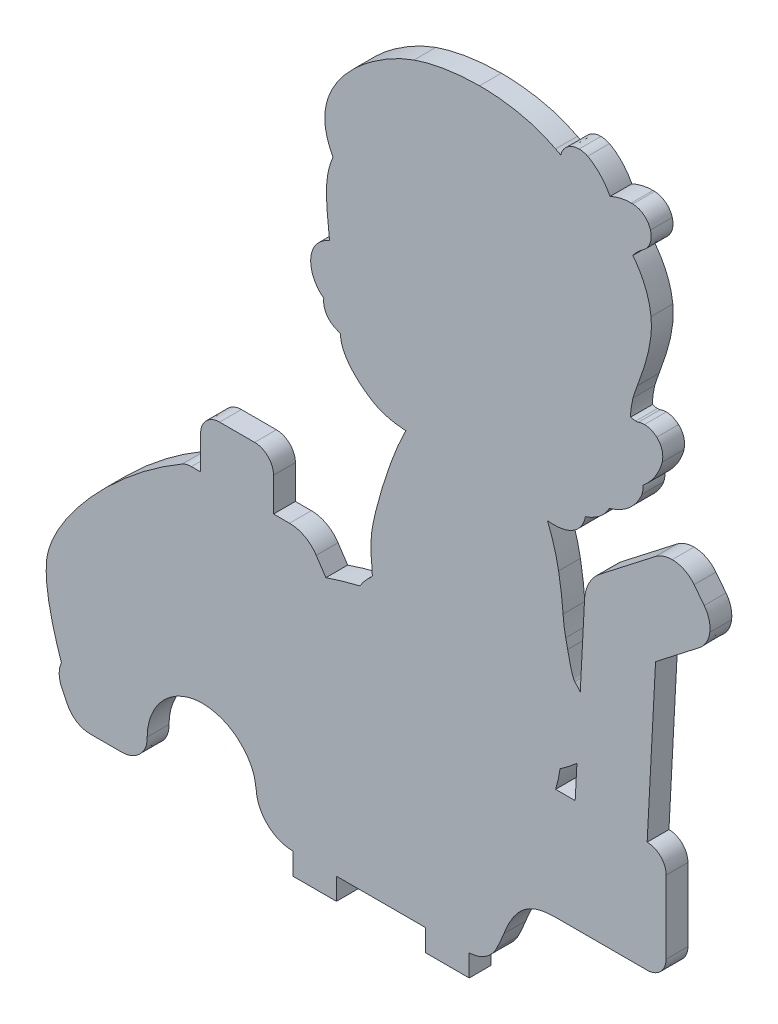
SolidWorks part; units mm, degrees
ref_plane "Front Plane" through (0, 0, 0) normal (0, 0, 1) x (1, 0, 0)
ref_plane "Top Plane" through (0, 0, 0) normal (0, 1, 0) x (1, 0, 0)
ref_plane "Right Plane" through (0, 0, 0) normal (1, 0, 0) x (0, 0, -1)
sketch "Model" plane through (0, 0, 0) normal (0, 0, 1) x (1, 0, 0)
  line L0 (289.9985, -383.7753) -> (289.8149, -387.2738)
  line L1 (289.8149, -387.2738) -> (287.7513, -387.2738)
  line L2 (263.5287, -380.0569) -> (262.5101, -378.5259)
  line L3 (259.6897, -377.0034) -> (258.0098, -377.0034)
  line L4 (258.0098, -377.0034) -> (258.0098, -373.459)
  line L5 (256.0138, -371.4557) -> (252.3171, -371.4557)
  line L6 (250.3211, -373.459) -> (250.3211, -377.0034)
  line L7 (250.3211, -377.0034) -> (249.3468, -377.0034)
  line L8 (235.6813, -404.0488) -> (236.2843, -405.2726)
  line L9 (238.6679, -406.7577) -> (242.0233, -406.7577)
  line L10 (260.043, -406.7577) -> (278.5385, -406.7577)
  line L11 (287.9321, -398.9652) -> (297.408, -398.9652)
  line L12 (299.404, -396.9619) -> (299.404, -389.2771)
  line L13 (297.408, -387.2738) -> (297.4036, -387.2738)
  line L14 (297.4036, -387.2738) -> (298.292, -370.3419)
  line L15 (298.292, -370.3419) -> (302.8973, -366.7692)
  line L16 (303.4169, -362.6517) -> (302.3566, -361.2835)
  line L17 (298.2586, -360.7635) -> (292.4293, -365.2857)
  line L18 (290.8054, -368.394) -> (290.3486, -377.102)
  line L19 (288.2912, -329.0773) -> (287.7488, -328.7908)
  spline S0 degree 3 poles (288.2176, -385.16) (288.7789, -384.7782) (289.421, -384.2968) (289.9985, -383.7753) knots 0 0 0 0 1 1 1 1
  spline S1 degree 3 poles (287.7513, -387.2738) (288.0017, -386.4926) (288.1406, -385.7436) (288.2176, -385.16) knots 3 3 3 3 4 4 4 4
  spline S2 degree 3 poles (279.7281, -327.0358) (277.2927, -327.0357) (274.84, -327.4258) (272.8218, -328.1341) knots 1 1 1 1 2 2 2 2
  spline S3 degree 3 poles (272.8218, -328.1341) (270.6039, -328.9125) (268.2296, -330.4012) (266.4707, -332.1165) knots 2 2 2 2 3 3 3 3
  spline S4 degree 3 poles (266.4707, -332.1165) (264.1293, -334.3998) (263.1008, -336.8128) (263.4964, -339.0948) knots 3 3 3 3 4 4 4 4
  spline S5 degree 3 poles (263.4964, -339.0948) (263.6216, -339.8165) (263.8794, -340.5475) (264.2658, -341.2784) knots 4 4 4 4 5 5 5 5
  spline S6 degree 3 poles (264.2658, -341.2784) (264.0578, -341.7935) (263.8519, -342.4295) (263.7162, -343.1598) knots 5 5 5 5 6 6 6 6
  spline S7 degree 3 poles (263.7162, -343.1598) (263.4474, -344.6049) (263.6585, -346.8017) (263.8775, -348.7474) knots 6 6 6 6 7 7 7 7
  spline S8 degree 3 poles (263.8775, -348.7474) (263.8922, -348.8774) (263.9055, -348.9946) (263.9165, -349.096) knots 7 7 7 7 8 8 8 8
  spline S9 degree 3 poles (263.9165, -349.096) (263.3073, -349.3249) (262.7745, -349.7324) (262.4163, -350.2673) knots 8 8 8 8 9 9 9 9
  spline S10 degree 3 poles (262.4163, -350.2673) (261.8528, -351.1083) (261.7663, -352.1733) (262.1788, -353.1892) knots 9 9 9 9 10 10 10 10
  spline S11 degree 3 poles (262.1788, -353.1892) (262.4294, -353.8064) (262.8184, -354.3024) (263.3046, -354.6489) knots 10 10 10 10 11 11 11 11
  spline S12 degree 3 poles (263.3046, -354.6489) (263.2765, -354.8621) (263.2826, -355.0805) (263.3246, -355.2958) knots 11 11 11 11 12 12 12 12
  spline S13 degree 3 poles (263.3246, -355.2958) (263.431, -355.841) (263.7581, -356.3175) (264.228, -356.6112) knots 12 12 12 12 13 13 13 13
  spline S14 degree 3 poles (264.228, -356.6112) (264.3474, -356.6859) (264.6348, -356.8483) (265.0896, -357.0027) knots 13 13 13 13 14 14 14 14
  spline S15 degree 3 poles (265.0896, -357.0027) (265.0758, -357.1622) (265.0811, -357.3246) (265.1067, -357.4867) knots 14 14 14 14 15 15 15 15
  spline S16 degree 3 poles (265.1067, -357.4867) (265.3252, -358.871) (266.6206, -360.3913) (268.5721, -361.5535) knots 15 15 15 15 16 16 16 16
  spline S17 degree 3 poles (268.5721, -361.5535) (269.4092, -362.052) (270.5449, -362.3431) (271.9558, -362.4217) knots 16 16 16 16 17 17 17 17
  spline S18 degree 3 poles (271.9558, -362.4217) (270.3159, -365.6075) (268.7289, -370.9204) (268.3692, -373.4038) knots 17 17 17 17 18 18 18 18
  spline S19 degree 3 poles (268.3692, -373.4038) (268.1946, -374.6086) (268.289, -375.6163) (268.3648, -376.426) knots 18 18 18 18 19 19 19 19
  spline S20 degree 3 poles (268.3648, -376.426) (268.4004, -376.8064) (268.4485, -377.3203) (268.4109, -377.507) knots 19 19 19 19 20 20 20 20
  spline S21 degree 3 poles (268.4109, -377.507) (268.41, -377.5078) (268.409, -377.5087) (268.408, -377.5096) knots 20 20 20 20 21 21 21 21
  spline S22 degree 3 poles (268.408, -377.5096) (267.8011, -378.0511) (267.3856, -378.557) (267.1083, -379.019) knots 21 21 21 21 22 22 22 22
  spline S23 degree 3 poles (267.1083, -379.019) (265.5866, -379.3829) (264.3897, -379.7552) (263.5287, -380.0569) knots 22 22 22 22 23 23 23 23
  spline S24 degree 3 poles (262.5101, -378.5259) (261.8831, -377.5723) (260.8296, -377.0034) (259.6897, -377.0034) knots 24 24 24 24 25 25 25 25
  spline S25 degree 3 poles (258.0098, -373.459) (258.0098, -372.3526) (257.1162, -371.4557) (256.0138, -371.4557) knots 27 27 27 27 28 28 28 28
  spline S26 degree 3 poles (252.3171, -371.4557) (251.2147, -371.4557) (250.3211, -372.3526) (250.3211, -373.459) knots 29 29 29 29 30 30 30 30
  spline S27 degree 3 poles (249.3468, -377.0034) (248.9989, -377.0034) (248.6571, -377.0947) (248.3552, -377.2681) knots 32 32 32 32 33 33 33 33
  spline S28 degree 3 poles (248.3552, -377.2681) (241.2374, -381.3575) (234.5679, -388.7784) (234.0825, -393.1489) knots 33 33 33 33 34 34 34 34
  spline S29 degree 3 poles (234.0825, -393.1489) (233.7752, -395.9163) (234.9563, -399.8057) (235.6424, -401.7681) knots 34 34 34 34 35 35 35 35
  spline S30 degree 3 poles (235.6424, -401.7681) (235.3136, -402.4919) (235.3233, -403.322) (235.6813, -404.0488) knots 35 35 35 35 36 36 36 36
  spline S31 degree 3 poles (236.2843, -405.2726) (236.7357, -406.1886) (237.649, -406.7577) (238.6679, -406.7577) knots 37 37 37 37 38 38 38 38
  spline S32 degree 3 poles (242.0233, -406.7577) (242.8394, -406.7577) (243.5707, -406.3871) (244.0588, -405.8049) knots 39 39 39 39 40 40 40 40
  spline S33 degree 3 poles (244.0588, -405.8049) (244.4475, -405.3412) (244.682, -404.8566) (244.682, -404.0353) knots 40 40 40 40 41 41 41 41
  spline S34 degree 3 poles (244.682, -404.0353) (244.721, -400.7145) (247.3433, -398.042) (250.4935, -398.042) knots 41 41 41 41 42 42 42 42
  spline S35 degree 3 poles (250.4935, -398.042) (252.901, -398.0452) (255.0156, -399.5006) (255.888, -401.7056) knots 42 42 42 42 43 43 43 43
  spline S36 degree 2 poles (255.888, -401.7056) (256.0262, -402.0573) (256.1904, -403.1653) knots 43 43 43 44 44 44
  spline S37 degree 3 poles (256.1904, -403.1653) (256.3332, -405.1702) (258.0066, -406.7577) (260.043, -406.7577) knots 44 44 44 44 45 45 45 45
  spline S38 degree 3 poles (278.5385, -406.7577) (279.7927, -406.7577) (280.9282, -406.0673) (281.502, -404.956) knots 46 46 46 46 47 47 47 47
  spline S39 degree 3 poles (281.502, -404.956) (281.7807, -404.4162) (282.0468, -403.8175) (282.2929, -403.1765) knots 47 47 47 47 48 48 48 48
  spline S40 degree 3 poles (282.2929, -403.1765) (283.76, -399.2895) (285.883, -398.9652) (287.9321, -398.9652) knots 48 48 48 48 49 49 49 49
  spline S41 degree 3 poles (297.408, -398.9652) (298.5103, -398.9652) (299.404, -398.0683) (299.404, -396.9619) knots 50 50 50 50 51 51 51 51
  spline S42 degree 3 poles (299.404, -389.2771) (299.404, -388.1707) (298.5103, -387.2738) (297.408, -387.2738) knots 52 52 52 52 53 53 53 53
  spline S43 degree 3 poles (302.8973, -366.7692) (303.5161, -366.2892) (303.9108, -365.5963) (304.0089, -364.8181) knots 56 56 56 56 57 57 57 57
  spline S44 degree 3 poles (304.0089, -364.8181) (304.107, -364.0402) (303.8967, -363.2709) (303.4169, -362.6517) knots 57 57 57 57 58 58 58 58
  spline S45 degree 3 poles (302.3566, -361.2835) (301.7986, -360.5635) (300.9568, -360.1506) (300.0471, -360.1506) knots 59 59 59 59 60 60 60 60
  spline S46 degree 3 poles (300.0471, -360.1506) (299.4033, -360.1506) (298.7682, -360.3682) (298.2586, -360.7635) knots 60 60 60 60 61 61 61 61
  spline S47 degree 3 poles (292.4293, -365.2857) (291.4615, -366.0364) (290.8697, -367.1693) (290.8054, -368.394) knots 62 62 62 62 63 63 63 63
  spline S48 degree 3 poles (290.3486, -377.102) (290.1562, -376.851) (289.9602, -376.6271) (289.772, -376.4388) knots 64 64 64 64 65 65 65 65
  spline S49 degree 3 poles (289.772, -376.4388) (289.4986, -376.1311) (289.212, -374.765) (289.0223, -373.861) knots 65 65 65 65 66 66 66 66
  spline S50 degree 3 poles (289.0223, -373.861) (288.9555, -373.5426) (288.8874, -373.2183) (288.8144, -372.8929) knots 66 66 66 66 67 67 67 67
  spline S51 degree 3 poles (288.8144, -372.8929) (288.642, -372.1245) (288.5985, -371.5998) (288.5381, -370.8736) knots 67 67 67 67 68 68 68 68
  spline S52 degree 3 poles (288.5381, -370.8736) (288.4675, -370.023) (288.3796, -368.9644) (288.0679, -367.1711) knots 68 68 68 68 69 69 69 69
  spline S53 degree 3 poles (288.0679, -367.1711) (287.8122, -365.7003) (287.366, -364.3239) (286.8927, -363.1609) knots 69 69 69 69 70 70 70 70
  spline S54 degree 3 poles (286.8927, -363.1609) (287.0416, -363.1791) (287.1753, -363.1899) (287.2918, -363.1959) knots 70 70 70 70 71 71 71 71
  spline S55 degree 3 poles (287.2918, -363.1959) (287.3941, -363.2011) (287.4917, -363.2036) (287.585, -363.2036) knots 71 71 71 71 72 72 72 72
  spline S56 degree 3 poles (287.585, -363.2036) (289.9033, -363.2036) (290.7438, -361.7222) (290.875, -360.8469) knots 72 72 72 72 73 73 73 73
  spline S57 degree 3 poles (290.875, -360.8469) (290.8775, -360.8303) (290.8798, -360.8136) (290.882, -360.797) knots 73 73 73 73 74 74 74 74
  spline S58 degree 3 poles (290.882, -360.797) (292.0577, -360.4417) (292.8744, -359.6931) (293.2711, -359.0262) knots 74 74 74 74 75 75 75 75
  spline S59 degree 3 poles (293.2711, -359.0262) (293.318, -358.9474) (293.3591, -358.8661) (293.3943, -358.783) knots 75 75 75 75 76 76 76 76
  spline S60 degree 3 poles (293.3943, -358.783) (293.4528, -358.7667) (293.511, -358.7498) (293.569, -358.7323) knots 76 76 76 76 77 77 77 77
  spline S61 degree 3 poles (293.569, -358.7323) (296.0101, -357.9939) (296.7701, -356.0179) (296.8488, -355.795) knots 77 77 77 77 78 78 78 78
  spline S62 degree 3 poles (296.8488, -355.795) (296.9513, -355.5043) (296.9891, -355.1985) (296.9622, -354.9012) knots 78 78 78 78 79 79 79 79
  spline S63 degree 3 poles (296.9622, -354.9012) (298.1733, -353.9098) (298.7918, -352.6042) (298.9896, -351.7798) knots 79 79 79 79 80 80 80 80
  spline S64 degree 3 poles (298.9896, -351.7798) (299.1632, -351.0562) (298.9762, -350.2768) (298.4188, -349.786) knots 80 80 80 80 81 81 81 81
  spline S65 degree 3 poles (298.4188, -349.786) (298.0425, -349.4547) (297.588, -349.2746) (297.1195, -349.2746) knots 81 81 81 81 82 82 82 82
  spline S66 degree 3 poles (297.1195, -349.2746) (296.9025, -349.2746) (296.6826, -349.3132) (296.466, -349.3933) knots 82 82 82 82 83 83 83 83
  spline S67 degree 3 poles (296.466, -349.3933) (296.4227, -349.402) (296.3247, -349.4182) (296.1972, -349.4182) knots 83 83 83 83 84 84 84 84
  spline S68 degree 3 poles (296.1972, -349.4182) (296.0085, -349.4182) (295.8332, -349.3836) (295.6743, -349.3152) knots 84 84 84 84 85 85 85 85
  spline S69 degree 3 poles (295.6743, -349.3152) (295.623, -349.011) (295.7022, -348.3839) (295.9104, -347.4465) knots 85 85 85 85 86 86 86 86
  spline S70 degree 3 poles (295.9104, -347.4465) (295.9612, -347.2177) (296.1733, -346.6388) (296.3604, -346.1281) knots 86 86 86 86 87 87 87 87
  spline S71 degree 3 poles (296.3604, -346.1281) (297.0823, -344.158) (298.0708, -341.4599) (297.813, -339.074) knots 87 87 87 87 88 88 88 88
  spline S72 degree 3 poles (297.813, -339.074) (297.5826, -336.9415) (296.623, -335.3648) (295.8968, -334.4484) knots 88 88 88 88 89 89 89 89
  spline S73 degree 3 poles (295.8968, -334.4484) (296.1152, -334.128) (296.5186, -333.703) (296.9482, -333.4073) knots 89 89 89 89 90 90 90 90
  spline S74 degree 3 poles (296.9482, -333.4073) (297.6676, -332.9237) (297.9899, -332.0327) (297.7527, -331.1969) knots 90 90 90 90 91 91 91 91
  spline S75 degree 3 poles (297.7527, -331.1969) (297.5154, -330.3611) (296.7639, -329.7771) (295.8986, -329.7467) knots 91 91 91 91 92 92 92 92
  spline S76 degree 3 poles (295.8986, -329.7467) (295.8411, -329.7447) (295.7838, -329.7437) (295.7269, -329.7437) knots 92 92 92 92 93 93 93 93
  spline S77 degree 3 poles (295.7269, -329.7437) (294.895, -329.7437) (294.1468, -329.9513) (293.4967, -330.2559) knots 93 93 93 93 94 94 94 94
  spline S78 degree 3 poles (293.4967, -330.2559) (292.8111, -328.9444) (291.8316, -328.1275) (291.1317, -327.7714) knots 94 94 94 94 95 95 95 95
  spline S79 degree 3 poles (291.1317, -327.7714) (290.8428, -327.6244) (290.5346, -327.5546) (290.2308, -327.5546) knots 95 95 95 95 96 96 96 96
  spline S80 degree 3 poles (290.2308, -327.5546) (289.5218, -327.5546) (288.8367, -327.9348) (288.4756, -328.6015) knots 96 96 96 96 97 97 97 97
  spline S81 degree 3 poles (288.4756, -328.6015) (288.3925, -328.7551) (288.3313, -328.915) (288.2912, -329.0773) knots 97 97 97 97 98 98 98 98
  spline S82 degree 3 poles (287.7488, -328.7908) (285.0019, -327.3404) (281.8709, -327.0359) (279.7281, -327.0358) knots 99 99 99 99 100 100 100 100
base flange "Base-Flange1" sketch "Model" thickness 2.3 reverse thickness direction no parameters "D1"=0.7366
sketch "Sketch6" plane through (0, 0, 0) normal (0, 0, 1) x (1, 0, 0)
  line L1 (260.043, -406.7577) -> (264.643, -406.7577)
  line L2 (260.043, -406.7577) -> (260.043, -409.0577)
  line L3 (260.043, -409.0577) -> (264.643, -409.0577)
  line L4 (264.643, -406.7577) -> (264.643, -409.0577)
  line L6 (278.643, -406.7577) -> (274.043, -406.7577)
  line L7 (278.643, -406.7577) -> (278.643, -409.0577)
  line L8 (278.643, -409.0577) -> (274.043, -409.0577)
  line L9 (274.043, -406.7577) -> (274.043, -409.0577)
  dimension "D1" = 2.3
  dimension "D2" = 4.6
  dimension "D3" = 9.4
  dimension "D4" = 4.6
  dimension "D5" = 2.3
base flange "Tab1" sketch "Sketch6" thickness 2.3 reverse thickness direction no parameters "D1"=0.7366
sketch "Bend-Lines1" [suppressed] plane through (0, 0, 0) normal (0, 1, 0) x (1, 0, 0)
sketch "Bounding-Box1" [suppressed] plane through (0, 0, 0) normal (0, 1, 0) x (1, 0, 0)
sheet metal parameters "Sheet-Metal1" thickness 2.3 parameters "D1"=0.7366
flat pattern "Flat-Pattern1" [suppressed]
sketch "Bend-Lines2" plane through (0, 0, 0) normal (0, 1, 0) x (1, 0, 0)
sketch3d "Bounding-Box2" [suppressed]
  line L0 (-20.5203, 0.3336, 0) -> (-20.5203, -79.3882, 0) construction
  line L1 (49.4794, 0.3336, 0) -> (49.4794, -79.3882, 0) construction
  line L2 (-20.5203, 0.3336, 0) -> (49.4794, 0.3336, 0) construction
  line L3 (-20.5203, -79.3882, 0) -> (49.4794, -79.3882, 0) construction
sheet metal parameters "Sheet-Metal2" thickness 2.3 parameters "D1"=0.7366
flat pattern "Flat-Pattern2"
sketch "Bend-Lines3" plane through (0, 0, 0) normal (0, 1, 0) x (1, 0, 0)
sketch3d "Bounding-Box3" [suppressed]
  line L0 (13.3278, -87.7129, 0) -> (25.4344, -2.835, 0) construction
  line L1 (-51.2466, -78.5022, 0) -> (-39.14, 6.3756, 0) construction
  line L2 (13.3278, -87.7129, 0) -> (-51.2466, -78.5022, 0) construction
  line L3 (25.4344, -2.835, 0) -> (-39.14, 6.3756, 0) construction
